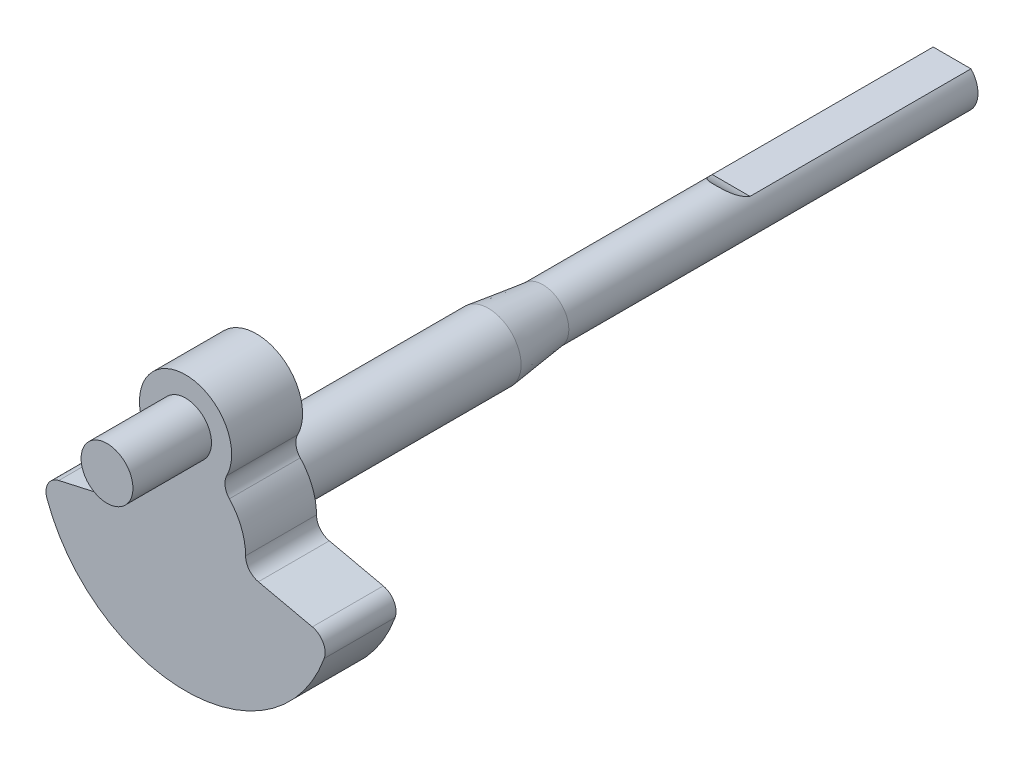
SolidWorks part; units mm, degrees
ref_plane "Front Plane" through (0, 0, 0) normal (0, 0, 1) x (1, 0, 0)
ref_plane "Top Plane" through (0, 0, 0) normal (0, 1, 0) x (1, 0, 0)
ref_plane "Right Plane" through (0, 0, 0) normal (1, 0, 0) x (0, 0, -1)
sketch "Sketch1" plane through (0, 0, 0) normal (0, 0, 1) x (1, 0, 0)
  line L0 (0, 19.5) -> (0, 0) construction
  line L1 (0, 19.5) -> (0, 27) construction
  line L2 (-23.237, -5.2003) -> (-13.3447, -2.9864)
  line L5 (13.3447, -2.9864) -> (23.237, -5.2003)
  arc A0 (-25.4045, -9.1438) -> (25.4045, -9.1438) centre (0, 0) ccw
  circle A1 centre (0, 0) radius 6
  arc A2 (-8.0251, 7.5231) -> (-10.9999, -0.0462) centre (0, 0) ccw
  circle A3 centre (0, 14.75) radius 4.75
  arc A4 (7.5377, 10.9308) -> (-7.5377, 10.9308) centre (0, 14.75) ccw
  arc A5 (10.9999, -0.0462) -> (8.0251, 7.5231) centre (0, 0) ccw
  arc A6 (25.4045, -9.1438) -> (23.237, -5.2003) centre (22.5818, -8.1278) ccw
  arc A7 (8.0251, 7.5231) -> (7.5377, 10.9308) centre (10.2138, 9.5749) cw
  arc A8 (13.3447, -2.9864) -> (10.9999, -0.0462) centre (13.9999, -0.0589) cw
  arc A9 (-23.237, -5.2003) -> (-25.4045, -9.1438) centre (-22.5818, -8.1278) ccw
  arc A10 (-13.3447, -2.9864) -> (-10.9999, -0.0462) centre (-13.9999, -0.0589) ccw
  arc A11 (-8.0251, 7.5231) -> (-7.5377, 10.9308) centre (-10.2138, 9.5749) ccw
  point P19 (10.7345, -2.4023)
  dimension "D1" = 54
  dimension "D2" = 12
  dimension "D3" = 5
  dimension "D4" = 19.5
  dimension "D5" = 9.5
  dimension "D6" = 3.7
  dimension "D7" = 3
extrude "Boss-Extrude1" add sketch "Sketch1" along normal blind 13
sketch "Sketch2" plane through (0, 0, 13) normal (0, 0, 1) x (1, 0, 0)
  circle A0 centre (0, 14.75) radius 4.75
extrude "Boss-Extrude2" add sketch "Sketch2" along normal blind 14.4 and the other way blind 13
sketch "Sketch3" plane through (0, 0, 13) normal (0, 0, 1) x (1, 0, 0)
  circle A0 centre (0, 0) radius 6
extrude "Boss-Extrude3" add sketch "Sketch3" against normal blind 55.5
sketch "Sketch4" plane through (0, 0, -42.5) normal (0, 0, -1) x (-1, 0, 0)
  circle A0 centre (0, 0) radius 4.75
  dimension "D1" = 9.5
extrude "Boss-Extrude4" add sketch "Sketch4" along normal blind 85
chamfer "Chamfer1" distance 1.25 distance2 10 1 edges at (-4.75, 0, -42.5) first distance on face at (-4.75, 0, -42.5)
sketch "Sketch5" plane through (0, 0, 0) normal (1, 0, 0) x (0, 0, -1)
  line L0 (127.5, 3.25) -> (87, 3.25)
  line L1 (127.5, -4.75) -> (127.5, 4.75) construction
  line L2 (127.5, 3.25) -> (127.5, 4.75)
  line L3 (127.5, 4.75) -> (127.5, 7.6782)
  line L4 (127.5, 7.6782) -> (81.9621, 7.6782)
  arc A0 (87, 3.25) -> (81.9621, 7.6782) centre (88.8609, 10.447) cw
  point P10 (81.9621, 8.0717)
  dimension "D1" = 40.5
  dimension "D2" = 1.5
extrude "Cut-Extrude1" cut sketch "Sketch5" against normal blind 15 and the other way blind 15
